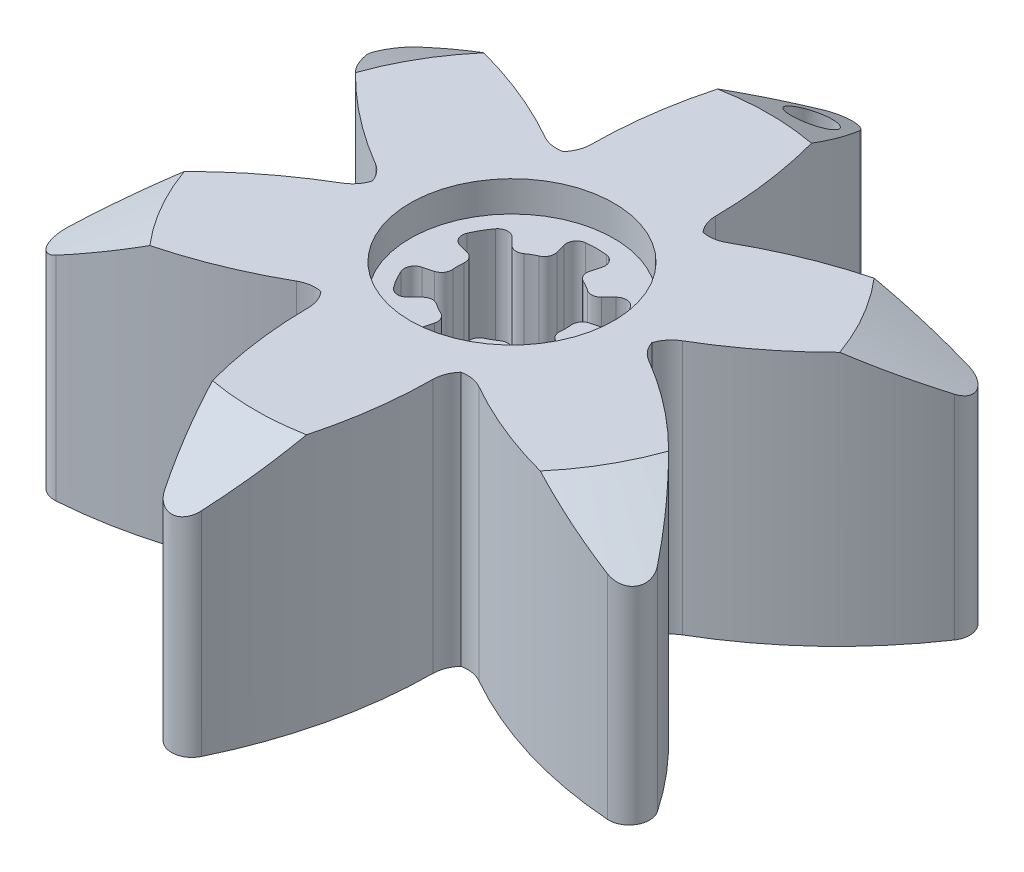
SolidWorks part; units mm, degrees
ref_plane "Front Plane" through (0, 0, 0) normal (0, 0, 1) x (1, 0, 0)
ref_plane "Top Plane" through (0, 0, 0) normal (0, 1, 0) x (1, 0, 0)
ref_plane "Right Plane" through (0, 0, 0) normal (1, 0, 0) x (0, 0, -1)
sketch "Sketch1" plane through (0, 0, 0) normal (0, 1, 0) x (1, 0, 0)
  circle A0 centre (0, 0) radius 17.8
  dimension "D1" = 35.6
extrude "Boss-Extrude1" add sketch "Sketch1" along normal blind 12.5
sketch "Sketch2" plane through (0, 12.5, 0) normal (0, 1, 0) x (1, 0, 0)
  line L3 (-3.05, 6.8) -> (-3.05, 6.0776)
  line L4 (6.7884, 0.3974) -> (7.414, 0.7586)
  line L5 (3.05, 6.0776) -> (3.05, 6.8)
  line L6 (4.364, 6.0414) -> (3.7384, 5.6802)
  line L7 (3.7384, -5.6802) -> (4.364, -6.0414)
  line L8 (7.414, -0.7586) -> (6.7884, -0.3974)
  line L9 (-3.05, -6.0776) -> (-3.05, -6.8)
  line L10 (3.05, -6.8) -> (3.05, -6.0776)
  line L11 (-6.7884, -0.3974) -> (-7.414, -0.7586)
  line L12 (-4.364, -6.0414) -> (-3.7384, -5.6802)
  line L13 (-3.7384, 5.6802) -> (-4.364, 6.0414)
  line L14 (-7.414, 0.7586) -> (-6.7884, 0.3974)
  circle A0 centre (0, 0) radius 6.8
  circle A1 centre (0, 0) radius 17.8 construction
  arc A2 (-3.05, 6.8) -> (0, 17.8) centre (18.3111, 6.8) cw
  arc A3 (0, 17.8) -> (3.05, 6.8) centre (-18.3111, 6.8) cw
  arc A4 (4.364, 6.0414) -> (15.4153, 8.9) centre (15.0445, -12.4578) cw
  arc A5 (15.4153, 8.9) -> (7.414, 0.7586) centre (-3.2666, 19.2578) cw
  arc A6 (7.414, -0.7586) -> (15.4153, -8.9) centre (-3.2666, -19.2578) cw
  arc A7 (15.4153, -8.9) -> (4.364, -6.0414) centre (15.0445, 12.4578) cw
  arc A8 (3.05, -6.8) -> (0, -17.8) centre (-18.3111, -6.8) cw
  arc A9 (0, -17.8) -> (-3.05, -6.8) centre (18.3111, -6.8) cw
  arc A10 (-4.364, -6.0414) -> (-15.4153, -8.9) centre (-15.0445, 12.4578) cw
  arc A11 (-15.4153, -8.9) -> (-7.414, -0.7586) centre (3.2666, -19.2578) cw
  arc A12 (-7.414, 0.7586) -> (-15.4153, 8.9) centre (3.2666, 19.2578) cw
  arc A13 (-15.4153, 8.9) -> (-4.364, 6.0414) centre (-15.0445, -12.4578) cw
  point P12 (0, 6.8)
  point P54 (0, 0)
  circle M8 centre (0, 0) radius 17.8
  dimension "D2" = 6.1
  dimension "D3" = 6
chamfer "Chamfer1" distance 3 angle 60 1 edges at (0, 12.5, 17.8) first distance on face at (0, 12.5, 17.8)
extrude "Cut-Extrude1" cut sketch "Sketch2" against normal through all contours L6 A4 A3 L5 A0 M8 | L8 A6 A5 L4 A0 M8 | L10 A8 A7 L7 A0 M8 | L12 A10 A9 L9 A0 M8 | L14 A12 A11 L11 A0 M8 | A13 L13 A0 L3 A2 M8 region at (-6.8858, 12.5, -11.9266) region at (6.8858, 12.5, -11.9266) region at (13.7717, 12.5, 0) region at (-13.7717, 12.5, 0) region at (-6.8858, 12.5, 11.9266) region at (6.8858, 12.5, 11.9266)
sketch "Sketch3" plane through (0, 12.5, 0) normal (0, 1, 0) x (1, 0, 0)
  line L1 (0.6859, 2.5597) -> (1.0741, 4.0086)
  line L3 (1.8738, 1.8738) -> (2.9345, 2.9345)
  line L5 (2.5597, 0.6859) -> (4.0086, 1.0741)
  line L7 (2.5597, -0.6859) -> (4.0086, -1.0741)
  line L9 (1.8738, -1.8738) -> (2.9345, -2.9345)
  line L11 (0.6859, -2.5597) -> (1.0741, -4.0086)
  line L13 (-0.6859, -2.5597) -> (-1.0741, -4.0086)
  line L15 (-1.8738, -1.8738) -> (-2.9345, -2.9345)
  line L17 (-2.5597, -0.6859) -> (-4.0086, -1.0741)
  line L19 (-2.5597, 0.6859) -> (-4.0086, 1.0741)
  line L21 (-1.8738, 1.8738) -> (-2.9345, 2.9345)
  line L23 (-0.6859, 2.5597) -> (-1.0741, 4.0086)
  circle A0 centre (0, 0) radius 5
  circle A1 centre (0, 0) radius 4.15
  arc A2 (-0.6859, 2.5597) -> (-1.8738, 1.8738) centre (0, 0) ccw
  arc A3 (1.8738, 1.8738) -> (0.6859, 2.5597) centre (0, 0) ccw
  arc A4 (2.5597, -0.6859) -> (2.5597, 0.6859) centre (0, 0) ccw
  arc A5 (0.6859, -2.5597) -> (1.8738, -1.8738) centre (0, 0) ccw
  arc A6 (-1.8738, -1.8738) -> (-0.6859, -2.5597) centre (0, 0) ccw
  arc A7 (-2.5597, 0.6859) -> (-2.5597, -0.6859) centre (0, 0) ccw
  point P31 (0, 0)
  dimension "D1" = 10
  dimension "D2" = 8.3
  dimension "D3" = 5.3
extrude "Cut-Extrude2" cut sketch "Sketch3" against normal through all contours L19 A7 L17 A1 L15 A6 L13 L11 A5 L9 L7 A4 L5 L3 A3 L1 L23 A2 L21 region at (0, 12.5, 0)
extrude "Cut-Extrude3" cut sketch "Sketch3<3>" against normal blind 1.5 contours A0 A1 | A3 L3 A1 L1 | A2 L23 A1 L21 | A7 L19 A1 L17 | A6 L15 A1 L13 | A5 L11 A1 L9 | A4 L7 A1 L5 region at (1.7079, 12.5, -2.9582) region at (-1.7079, 12.5, -2.9582) region at (3.4158, 12.5, 0) region at (-3.4158, 12.5, 0) region at (1.7079, 12.5, 2.9582) region at (-1.7079, 12.5, 2.9582) region at (-4.8586, 12.5, 0)
sketch "Sketch3<3>" plane through (0, 12.5, 0) normal (0, 1, 0) x (1, 0, 0) same geometry as "Sketch3"
fillet "Fillet1" radius 1 6 edges at (-15.4153, 4.75, 8.9) (-15.4153, 4.75, -8.9) (0, 4.75, -17.8) (15.4153, 4.75, -8.9) (0, 4.75, 17.8) (15.4153, 4.75, 8.9)
fillet "Fillet2" radius 1.5 12 edges at (3.05, 6.25, 6.0776) (3.7384, 6.25, 5.6802) (-3.7384, 6.25, 5.6802) (-3.05, 6.25, 6.0776) (-6.7884, 6.25, -0.3974) (-6.7884, 6.25, 0.3974) (-3.05, 6.25, -6.0776) (-3.7384, 6.25, -5.6802) (6.7884, 6.25, -0.3974) (6.7884, 6.25, 0.3974) (3.7384, 6.25, -5.6802) (3.05, 6.25, -6.0776)
sketch "Sketch4" plane through (0, 0, 0) normal (0, -1, 0) x (1, 0, 0)
  line L0 (0, 16.7038) -> (0, 15.3038)
  line L14 (6.0917, 0.3175) -> (4.9899, 0.3175)
  line L15 (6.0917, -0.3175) -> (4.9899, -0.3175)
  line L16 (2.5, 4.9652) -> (2.7709, 5.4344)
  line L17 (2.7709, 5.4344) -> (2.22, 4.4802)
  line L18 (3.3209, 5.1168) -> (2.77, 4.1626)
  line L19 (3.05, 4.6477) -> (3.3209, 5.1168)
  line L20 (3.3209, -5.1168) -> (2.77, -4.1626)
  line L21 (2.7709, -5.4344) -> (2.22, -4.4802)
  line L22 (-2.7709, -5.4344) -> (-2.22, -4.4802)
  line L23 (-3.3209, -5.1168) -> (-2.77, -4.1626)
  line L24 (-6.0917, -0.3175) -> (-4.9899, -0.3175)
  line L25 (-6.0917, 0.3175) -> (-4.9899, 0.3175)
  line L26 (-3.3209, 5.1168) -> (-2.77, 4.1626)
  line L27 (-2.7709, 5.4344) -> (-2.22, 4.4802)
  circle A0 centre (0, 0) radius 4.1
  circle A1 centre (0, 0) radius 5
  arc A2 (0.8993, 16.1411) -> (-0.8993, 16.1411) centre (0, 15.7038) ccw construction
  arc A3 (-6.0788, 0.5075) -> (-6.0788, -0.5075) centre (0, 0) ccw
  arc A4 (-2.0263, 6.4025) -> (-0.1836, 14.8895) centre (20.5583, 5.9426) cw
  arc A5 (0.1836, 14.8895) -> (2.0263, 6.4025) centre (-20.5583, 5.9426) cw
  arc A6 (0.1836, 14.8895) -> (-0.1836, 14.8895) centre (0, 14.8103) ccw
  arc A7 (4.5316, 4.9561) -> (12.8029, 7.6038) centre (15.4256, -14.8327) cw
  arc A8 (12.9865, 7.2857) -> (12.8029, 7.6038) centre (12.8261, 7.4052) ccw
  arc A9 (12.9865, 7.2857) -> (6.5579, 1.4464) centre (-5.1327, 20.7754) cw
  arc A10 (6.5579, -1.4464) -> (12.9865, -7.2857) centre (-5.1327, -20.7754) cw
  arc A11 (12.8029, -7.6038) -> (12.9865, -7.2857) centre (12.8261, -7.4052) ccw
  arc A12 (12.8029, -7.6038) -> (4.5316, -4.9561) centre (15.4256, 14.8327) cw
  arc A13 (2.0263, -6.4025) -> (0.1836, -14.8895) centre (-20.5583, -5.9426) cw
  arc A14 (-0.1836, -14.8895) -> (0.1836, -14.8895) centre (0, -14.8103) ccw
  arc A15 (-0.1836, -14.8895) -> (-2.0263, -6.4025) centre (20.5583, -5.9426) cw
  arc A16 (-4.5316, -4.9561) -> (-12.8029, -7.6038) centre (-15.4256, 14.8327) cw
  arc A17 (-12.9865, -7.2857) -> (-12.8029, -7.6038) centre (-12.8261, -7.4052) ccw
  arc A18 (-12.9865, -7.2857) -> (-6.5579, -1.4464) centre (5.1327, -20.7754) cw
  arc A19 (-6.5579, 1.4464) -> (-12.9865, 7.2857) centre (5.1327, 20.7754) cw
  arc A20 (-12.8029, 7.6038) -> (-12.9865, 7.2857) centre (-12.8261, 7.4052) ccw
  arc A21 (-12.8029, 7.6038) -> (-4.5316, 4.9561) centre (-15.4256, -14.8327) cw
  arc A22 (-2.5999, 5.5182) -> (-3.479, 5.0107) centre (0, 0) ccw
  arc A23 (3.479, 5.0107) -> (2.5999, 5.5182) centre (0, 0) ccw
  arc A24 (6.0788, -0.5075) -> (6.0788, 0.5075) centre (0, 0) ccw
  arc A25 (2.5999, -5.5182) -> (3.479, -5.0107) centre (0, 0) ccw
  arc A26 (-3.479, -5.0107) -> (-2.5999, -5.5182) centre (0, 0) ccw
  arc A28 (-2.5999, 5.5182) -> (-2.0263, 6.4025) centre (-3.0261, 6.4228) ccw
  arc A29 (6.0788, 0.5075) -> (6.5579, 1.4464) centre (7.0754, 0.5907) cw
  arc A30 (3.479, 5.0107) -> (4.5316, 4.9561) centre (4.0493, 5.8321) ccw
  arc A31 (3.479, -5.0107) -> (4.5316, -4.9561) centre (4.0493, -5.8321) cw
  arc A32 (6.0788, -0.5075) -> (6.5579, -1.4464) centre (7.0754, -0.5907) ccw
  arc A33 (-2.5999, -5.5182) -> (-2.0263, -6.4025) centre (-3.0261, -6.4228) cw
  arc A34 (2.5999, -5.5182) -> (2.0263, -6.4025) centre (3.0261, -6.4228) ccw
  arc A35 (-6.0788, -0.5075) -> (-6.5579, -1.4464) centre (-7.0754, -0.5907) cw
  arc A36 (-3.479, -5.0107) -> (-4.5316, -4.9561) centre (-4.0493, -5.8321) ccw
  arc A37 (-3.479, 5.0107) -> (-4.5316, 4.9561) centre (-4.0493, 5.8321) cw
  arc A38 (-6.0788, 0.5075) -> (-6.5579, 1.4464) centre (-7.0754, 0.5907) ccw
  arc A39 (2.0263, 6.4025) -> (2.5999, 5.5182) centre (3.0261, 6.4228) ccw
  point P28 (2.775, 4.8064)
  point P68 (0, 0)
  point P103 (0, 0)
  point P110 (0, 0)
  dimension "D1" = 10
  dimension "D2" = 8.2
  dimension "D4" = 12.2
  dimension "D5" = 0.2
  dimension "D7" = 1
  dimension "D3" = 1.4
  dimension "D6" = 6
  dimension "D9" = 6
  dimension "D8" = 6
extrude "Cut-Extrude4" cut sketch "Sketch4" against normal blind 9 and the other way through all contours A39 A5 A6 A4 A28 A22 L27 A1 L17 L16 A23 | A38 A3 L25 A1 L26 A22 A37 A21 A20 A19 | A36 A26 L23 A1 L24 A3 A35 A18 A17 A16 | A34 A25 L21 A1 L22 A26 A33 A15 A14 A13 | A32 A24 L15 A1 L20 A25 A31 A12 A11 A10 | A30 A23 L18 A1 L14 A24 A29 A9 A8 A7 region at (7.5517, 0, 4.36) region at (7.5517, 0, -4.36) region at (0, 0, 8.7199) region at (0, 0, -8.7199) region at (-7.5517, 0, 4.36) region at (-7.5517, 0, -4.36)
sketch "Sketch5" plane through (0, 12.5, 0) normal (0, 1, 0) x (1, 0, 0)
  line L0 (0, 16.7038) -> (0, 14.7038)
  arc A0 (0.8993, 16.1411) -> (-0.8993, 16.1411) centre (0, 15.7038) ccw construction
  circle A1 centre (0, 14.7038) radius 1
  dimension "D2" = 2
  dimension "D1" = 2
extrude "Cut-Extrude5" cut sketch "Sketch5" against normal through all contours A1 region at (-0.6871, 12.5, -14.0167)
fillet "Fillet3" radius 0.5 24 edges at (4.0086, 5.5, -1.0741) (2.9345, 5.5, -2.9345) (1.8738, 5.5, -1.8738) (-1.0741, 5.5, -4.0086) (0.6859, 5.5, -2.5597) (1.0741, 5.5, -4.0086) (4.0086, 5.5, 1.0741) (2.5597, 5.5, 0.6859) (2.5597, 5.5, -0.6859) (1.0741, 5.5, 4.0086) (2.9345, 5.5, 2.9345) (1.8738, 5.5, 1.8738) (0.6859, 5.5, 2.5597) (-2.9345, 5.5, 2.9345) (-1.0741, 5.5, 4.0086) (-0.6859, 5.5, 2.5597) (-1.8738, 5.5, 1.8738) (-4.0086, 5.5, 1.0741) (-2.5597, 5.5, 0.6859) (-2.5597, 5.5, -0.6859) (-4.0086, 5.5, -1.0741) (-2.9345, 5.5, -2.9345) (-1.8738, 5.5, -1.8738) (-0.6859, 5.5, -2.5597)
